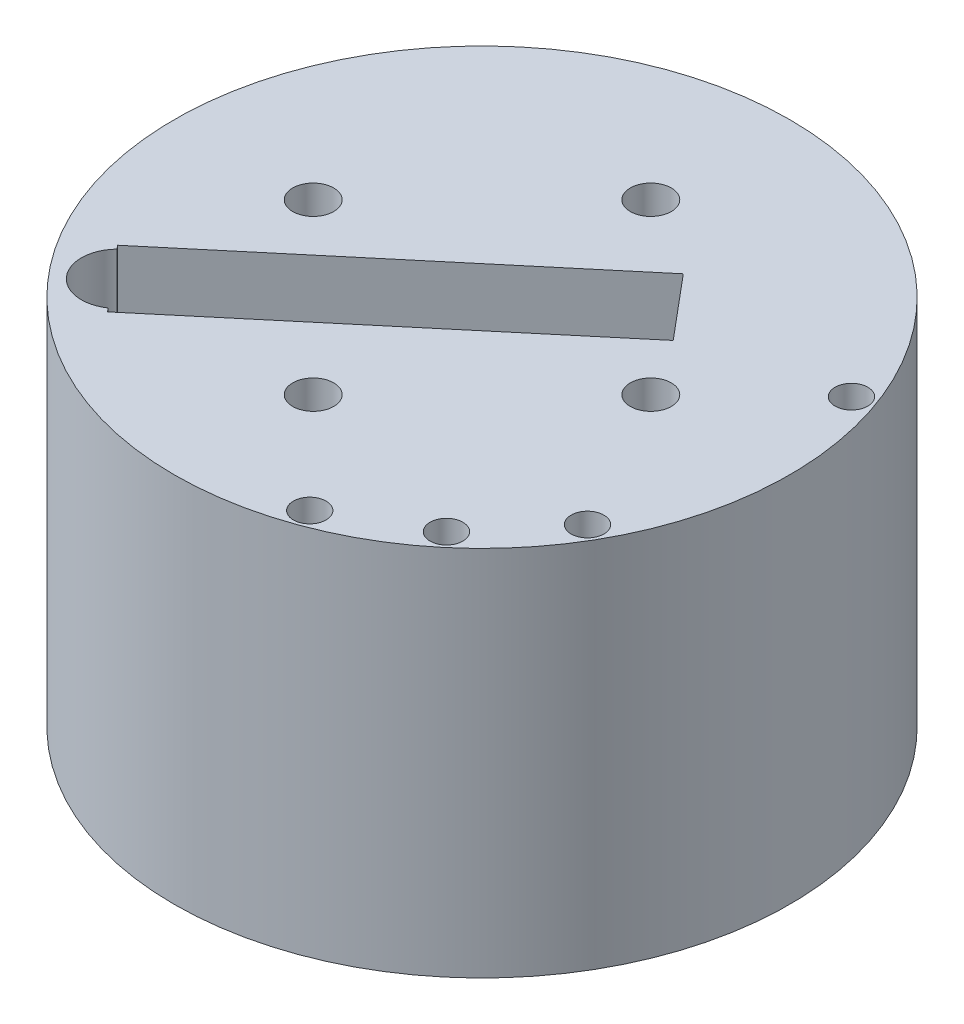
SolidWorks part; units mm, degrees
ref_plane "Front Plane" through (0, 0, 0) normal (0, 0, 1) x (1, 0, 0)
ref_plane "Top Plane" through (0, 0, 0) normal (0, 1, 0) x (1, 0, 0)
ref_plane "Right Plane" through (0, 0, 0) normal (1, 0, 0) x (0, 0, -1)
sketch "Sketch2" plane through (0, 0, 0) normal (0, 1, 0) x (1, 0, 0)
  circle A0 centre (0, 0) radius 47.6885
  dimension "D1" = 95.377
extrude "Boss-Extrude1" add sketch "Sketch2" along normal blind 57.658
sketch "Sketch4" plane through (0, 57.658, 0) normal (0, 1, 0) x (1, 0, 0)
  circle A1 centre (-26.162, 0) radius 3.175
  circle A2 centre (26.162, 0) radius 3.175
  circle A3 centre (0, 26.162) radius 3.175
  circle A4 centre (0, -26.162) radius 3.175
sketch "Sketch5" plane through (0, 57.658, 0) normal (0, 1, 0) x (1, 0, 0)
  line L2 (0, 0) -> (-42.4665, -13.8681)
  line L4 (0, 0) -> (-30.6943, -25.7555)
  circle A2 centre (0, 0) radius 44.6736
  circle A9 centre (-30.6943, -25.7555) radius 5.6388
  dimension "D3" = 11.2776
  dimension "D5" = 89.3472
  dimension "D6" = 21.915
  dimension "D4" = 40.0685
extrude "Cut-Extrude2" cut sketch "Sketch5" against normal through all contours A9
extrude "Cut-Extrude3" cut sketch "Sketch4" against normal through all
sketch "Sketch6" plane through (0, 57.658, 0) normal (0, 1, 0) x (1, 0, 0)
  line L1 (-27.0503, -30.9873) -> (20.6206, 9.0134)
  line L2 (-27.0503, -30.9873) -> (-35.2137, -21.2585)
  line L3 (-35.2137, -21.2585) -> (12.4572, 18.7422)
  line L4 (20.6206, 9.0134) -> (12.4572, 18.7422)
  dimension "D1" = 62.23
  dimension "D2" = 12.7
  dimension "D3" = 6.35
  dimension "D4" = 21.59
  dimension "D5" = 90
  dimension "D6" = 90
  dimension "D7" = 90
extrude "Cut-Extrude4" cut sketch "Sketch6" against normal blind 43.18
sketch "Sketch11" plane through (0, 0, 0) normal (0, -1, 0) x (1, 0, 0)
  circle A0 centre (0, 26.162) radius 6.35
  circle A1 centre (26.162, 0) radius 6.35
  circle A2 centre (0, -26.162) radius 6.35
  circle A3 centre (-26.162, 0) radius 6.35
  dimension "D1" = 12.7
  dimension "D2" = 12.7
  dimension "D3" = 12.7
  dimension "D4" = 12.7
extrude "Cut-Extrude7" cut sketch "Sketch11" against normal blind 7.62
sketch "Sketch14" plane through (0, 0, 0) normal (0, -1, 0) x (1, 0, 0)
  circle A0 centre (1.3569, -14.949) radius 2.067
  circle A1 centre (4.5237, 8.9723) radius 2.067
extrude "Cut-Extrude8" cut sketch "Sketch14" against normal blind 19.05
sketch "Sketch15" plane through (0, 0, 0) normal (0, -1, 0) x (1, 0, 0)
  line L0 (47.6885, 0) -> (-47.6885, 0)
  line L1 (0, -47.6885) -> (0, 47.6885)
  line L2 (-30.6943, 25.7555) -> (0, 0)
  line L3 (0, 0) -> (-44.6487, -1.4926) construction
  line L4 (0, 0) -> (-41.4455, -16.6734) construction
  line L5 (0, 0) -> (28.7156, 34.222)
  line L6 (0, 0) -> (38.6885, 22.3368)
  line L7 (0, 0) -> (15.2793, 41.9794)
  line L8 (0, 0) -> (41.9794, -15.2793)
  circle A0 centre (0, 0) radius 47.6885 construction
  circle A1 centre (1.3569, -14.949) radius 2.067 construction
  circle A2 centre (1.3569, -14.949) radius 2.067 construction
  circle A3 centre (4.5237, 8.9723) radius 2.067 construction
  circle A4 centre (28.7156, 34.222) radius 2.54
  circle A5 centre (38.6885, 22.3368) radius 2.54
  circle A6 centre (15.2793, 41.9794) radius 2.54
  circle A7 centre (41.9794, -15.2793) radius 2.54
  point P9 (0, 0)
  dimension "D1" = 1.3569
  dimension "D2" = 14.949
  dimension "D3" = 8.9723
  dimension "D4" = 4.5237
  dimension "D6" = 40
  dimension "D7" = 44.6736
  dimension "D10" = 50
  dimension "D5" = 40.0685
  dimension "D8" = 20
  dimension "D9" = 20
extrude "Cut-Extrude10" cut sketch "Sketch15" against normal blind 84.074 contours A4 | A6 | A5 | A7
equation "\"D4@Sketch5\"=(3.755/2)-(0.5/2)-0.05"
equation "\"D1@Sketch6\"=2.10 + (0.85-0.5)"
